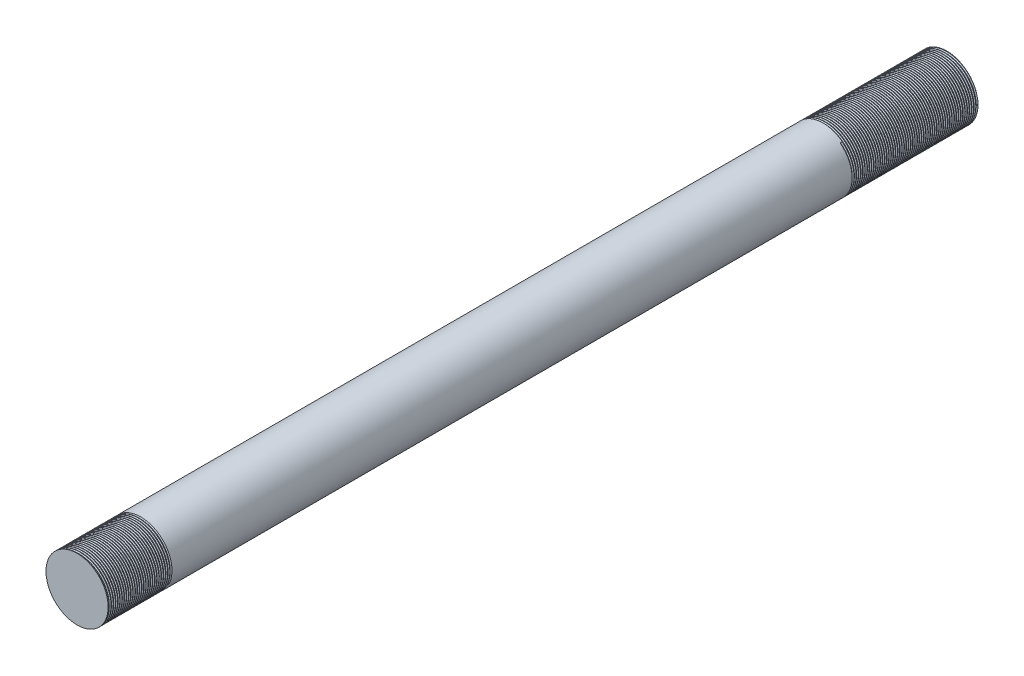
SolidWorks part; units mm, degrees
ref_plane "Спереди" through (0, 0, 0) normal (0, 0, 1) x (1, 0, 0)
ref_plane "Сверху" through (0, 0, 0) normal (0, 1, 0) x (1, 0, 0)
ref_plane "Справа" through (0, 0, 0) normal (1, 0, 0) x (0, 0, -1)
other "Configuration Table"
sketch "Sketch1" plane through (0, 0, 0) normal (0, 0, 1) x (1, 0, 0)
  circle A0 centre (0, 0) radius 5
  dimension "D1" = 10
extrude "Boss-Extrude1" add sketch "Sketch1" along normal blind 140
thread "Thread1" pitch 0.35 method cut profile "Thread Profile1" start angle 0, offset 0, length 10, pitch 0.35, diameter 10
ref_plane "Plane1" through (-5, 0, 140) normal (0, -1, 0) x (-1, 0, 0)
sketch "Thread Profile1" plane through (-5, 0, 140) normal (0, -1, 0) x (-1, 0, 0)
  line L0 (0, 0) -> (0, 0.35) construction
  line L11 (0, 0) -> (0, 0.3062)
  line L12 (0, 0.3062) -> (-0.1894, 0.1969)
  line L13 (-0.1894, 0.1969) -> (-0.1894, 0.1094)
  line L15 (-0.1894, 0.1094) -> (0, 0)
  line L17 (-0.1894, 0.1531) -> (0, 0.1531) construction
  point P2 (0, 0)
  dimension "Pitch" = 0.35
  dimension "Profile_Angle" = 60
  dimension "Profile_Land" = 0.0875
  dimension "Profile_Height" = 0.1894
thread "Thread2" pitch 0.35 method cut profile "Thread Profile2" start angle 0, offset 0, length 20, pitch 0.35, diameter 10
ref_plane "Plane2" through (5, 0, 0) normal (0, -1, 0) x (1, 0, 0)
sketch "Thread Profile2" plane through (5, 0, 0) normal (0, -1, 0) x (1, 0, 0)
  line L0 (0, 0) -> (0, 0.35) construction
  line L11 (0, 0) -> (0, 0.3062)
  line L12 (0, 0.3062) -> (-0.1894, 0.1969)
  line L13 (-0.1894, 0.1969) -> (-0.1894, 0.1094)
  line L15 (-0.1894, 0.1094) -> (0, 0)
  line L17 (-0.1894, 0.1531) -> (0, 0.1531) construction
  point P2 (0, 0)
  dimension "Pitch" = 0.35
  dimension "Profile_Angle" = 60
  dimension "Profile_Land" = 0.0875
  dimension "Profile_Height" = 0.1894
ref_axis "Axis1" through (0, 0, 118.0226) along (0, 0, -1)
